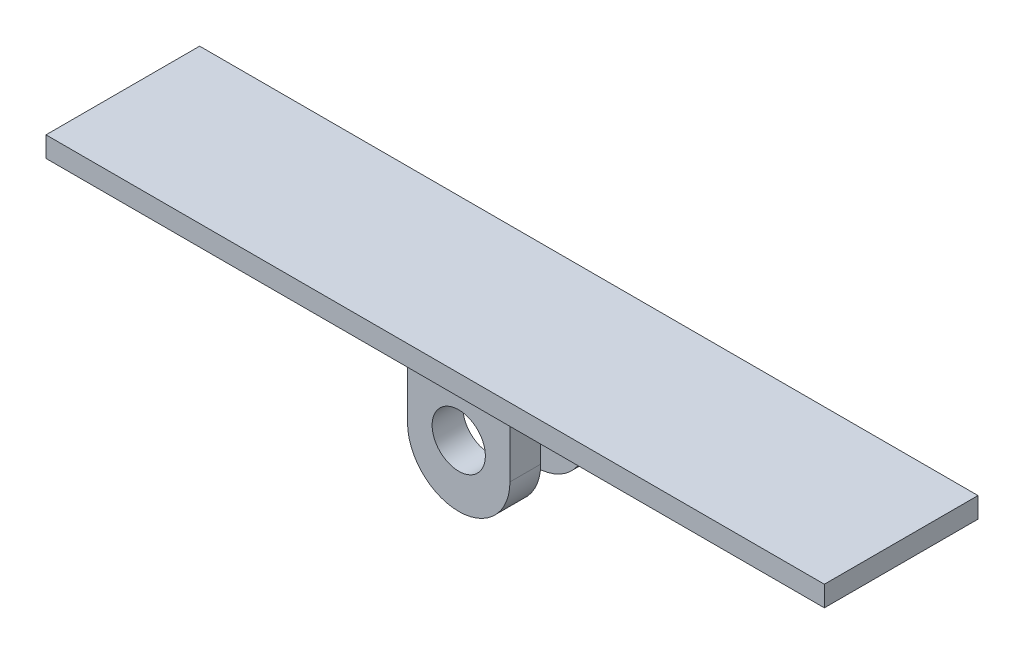
SolidWorks part; units mm, degrees
material "PE High Density"
ref_plane "Front Plane" through (0, 0, 0) normal (1, 0, 0) x (0, 1, 0)
ref_plane "Top Plane" through (0, 0, 0) normal (0, 0, 1) x (0, 1, 0)
ref_plane "Right Plane" through (0, 0, 0) normal (0, 1, 0) x (-1, 0, 0)
sketch "Sketch1" plane through (0, 0, 0) normal (0, 0, 1) x (0, 1, 0)
  line L1 (-1, 38) -> (1, 38)
  line L2 (-1, 38) -> (-1, -38)
  line L3 (-1, -38) -> (1, -38)
  line L4 (1, 38) -> (1, -38)
  line L5 (-1, 38) -> (1, -38) construction
  line L6 (-1, -38) -> (1, 38) construction
  point P0 (0, 0)
  dimension "D1" = 2
  dimension "D2" = 76
extrude "Boss-Extrude1" add sketch "Sketch1" against normal blind 15
sketch "Sketch2" plane through (0, -1, 0) normal (0, -1, 0) x (1, 0, 0)
  line L0 (0, 0) -> (0, -15) construction
  line L1 (-38, -15) -> (38, -15) construction
  line L2 (-38, -7.5) -> (38, -7.5) construction
  line L3 (-38, -15) -> (-38, 0) construction
  line L4 (38, -15) -> (38, 0) construction
  line L5 (38, 0) -> (-38, 0) construction
  line L6 (-5, -2.3) -> (5, -2.3)
  line L7 (-5, -2.3) -> (-5, -5.3)
  line L8 (-5, -5.3) -> (5, -5.3)
  line L9 (5, -2.3) -> (5, -5.3)
  line L10 (-5, -2.3) -> (5, -5.3) construction
  line L11 (-5, -5.3) -> (5, -2.3) construction
  line L12 (-5, -9.8) -> (5, -9.8)
  line L13 (-5, -9.8) -> (-5, -12.8)
  line L14 (-5, -12.8) -> (5, -12.8)
  line L15 (5, -9.8) -> (5, -12.8)
  line L16 (-5, -9.8) -> (5, -12.8) construction
  line L17 (-5, -12.8) -> (5, -9.8) construction
  point P11 (0, -3.8)
  point P16 (0, -11.3)
  dimension "D1" = 10
  dimension "D2" = 10
  dimension "D3" = 4.5
  dimension "D4" = 2.3
  dimension "D5" = 11.2
  dimension "D6" = 3
extrude "Boss-Extrude2" add sketch "Sketch2" along normal blind 12
sketch "Sketch3" plane through (0, 0, -2.3) normal (0, 0, 1) x (1, 0, 0)
  line L0 (0, -13) -> (0, 0) construction
  line L1 (5, -13) -> (-5, -13) construction
  line L2 (5, -13) -> (5, -1) construction
  line L3 (5, -7) -> (-5, -7) construction
  line L4 (-5, -13) -> (-5, -1) construction
  circle A0 centre (0, -7) radius 2.6
  dimension "D1" = 5.2
extrude "Cut-Extrude1" cut sketch "Sketch3" against normal blind 12
fillet "Fillet1" radius 5 4 edges at (-5, -13, -11.3) (5, -13, -11.3) (5, -13, -3.8) (-5, -13, -3.8)
scale "Scale1" scale about centroid uniform scaling yes scale factor 0.7
sketch "Sketch4" plane through (0, 0, -13.4528) normal (0, 0, -1) x (-1, 0, 0)
  circle A0 centre (0, 11.066) radius 1
  dimension "D1" = 2
